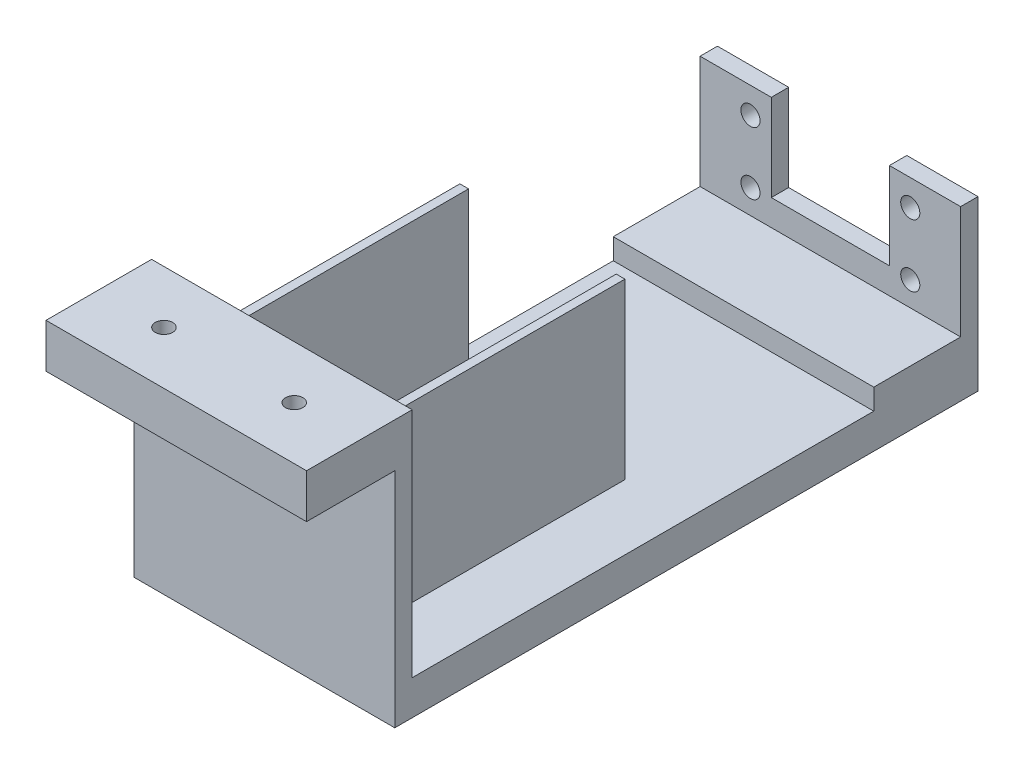
SolidWorks part; units mm, degrees
material "ABS"
ref_plane "Front Plane" through (0, 0, 0) normal (0, 0, 1) x (1, 0, 0)
ref_plane "Top Plane" through (0, 0, 0) normal (0, 1, 0) x (1, 0, 0)
ref_plane "Right Plane" through (0, 0, 0) normal (1, 0, 0) x (0, 0, -1)
sketch "Sketch1" plane through (0, 0, 0) normal (0, 0, 1) x (1, 0, 0)
  line L0 (20.5, 32.5) -> (20.5, 7.5)
  line L1 (0, 0) -> (75, 0)
  line L2 (0, 0) -> (0, 32.5)
  line L3 (0, 32.5) -> (75, 32.5)
  line L4 (75, 0) -> (75, 32.5)
  line L5 (20.5, 7.5) -> (54.5, 7.5)
  line L6 (54.5, 7.5) -> (54.5, 32.5)
  line L7 (37.5, 32.5) -> (37.5, 0) construction
  circle A0 centre (14.5, 25) radius 2.75
  circle A1 centre (14.5, 7) radius 2.75
  circle A2 centre (60.5, 7) radius 2.75
  circle A3 centre (60.5, 25) radius 2.75
  dimension "D6" = 5.5
  dimension "D7" = 46
  dimension "D8" = 34
  dimension "D1" = 32.5
  dimension "D2" = 75
  dimension "D3" = 17
  dimension "D4" = 18
  dimension "D5" = 25
  dimension "D9" = 25
  dimension "D10" = 14.5
  dimension "D11" = 6
extrude "Boss-Extrude1" add sketch "Sketch1" along normal blind 5 contours L7 L5 L0 L3 L2 L1 A1 A0 | L5 L7 L1 L4 L3 L6 A3 A2 region at (13.183, 14.1302, 0) region at (61.817, 14.1302, 0)
sketch "Sketch2" plane through (0, 0, 5) normal (0, 0, 1) x (1, 0, 0)
  line L0 (75, 0) -> (75, 32.5) construction
  line L1 (0, 0) -> (75, 0)
  line L2 (0, 0) -> (0, -6)
  line L3 (0, -6) -> (75, -6)
  line L4 (75, 0) -> (75, -6)
  dimension "D1" = 6
extrude "Boss-Extrude2" add sketch "Sketch2" along normal blind 25 and the other way blind 5
sketch "Sketch3" plane through (0, 0, 0) normal (0, 0, -1) x (-1, 0, 0)
  line L0 (0, -6) -> (0, 32.5) construction
  line L1 (-75, -6) -> (0, -6)
  line L2 (-75, -6) -> (-75, -16)
  line L3 (-75, -16) -> (0, -16)
  line L4 (0, -6) -> (0, -16)
  dimension "D1" = 10
extrude "Boss-Extrude3" add sketch "Sketch3" against normal blind 167.8942
sketch "Sketch4" plane through (0, -6, 0) normal (0, 1, 0) x (1, 0, 0)
  line L0 (75, -167.8942) -> (75, -30) construction
  line L1 (0, -167.8942) -> (75, -167.8942)
  line L2 (0, -167.8942) -> (0, -162.8942)
  line L3 (0, -162.8942) -> (75, -162.8942)
  line L4 (75, -167.8942) -> (75, -162.8942)
  dimension "D1" = 5
extrude "Boss-Extrude4" add sketch "Sketch4" along normal blind 66.8
sketch "Sketch5" plane through (0, 0, 167.8942) normal (0, 0, 1) x (1, 0, 0)
  line L0 (0, -16) -> (0, 60.8) construction
  line L1 (0, 48.1) -> (75, 48.1)
  line L2 (0, 48.1) -> (0, 60.8)
  line L3 (0, 60.8) -> (75, 60.8)
  line L4 (75, 48.1) -> (75, 60.8)
  line L5 (75, 60.8) -> (75, -16) construction
  line L6 (0, 60.8) -> (75, 60.8) construction
  dimension "D2" = 12.7
extrude "Boss-Extrude5" add sketch "Sketch5" along normal blind 25.4
sketch "Sketch6" plane through (0, 60.8, 0) normal (0, 1, 0) x (1, 0, 0)
  line L0 (0, -178.0942) -> (37.5, -178.0942) construction
  line L1 (37.5, -193.2942) -> (37.5, -162.8942) construction
  line L2 (75, -178.0942) -> (37.5, -178.0942) construction
  line L5 (0, -162.8942) -> (0, -193.2942)
  line L6 (0, -193.2942) -> (75, -193.2942)
  line L7 (75, -193.2942) -> (75, -162.8942)
  line L9 (0, -162.8942) -> (0, -193.2942)
  line L10 (0, -193.2942) -> (75, -193.2942)
  line L11 (75, -193.2942) -> (75, -162.8942)
  line L40 (75, -162.8942) -> (0, -162.8942)
  line L41 (75, -162.8942) -> (0, -162.8942)
  point P4 (18.75, -178.0942)
  point P10 (56.25, -178.0942)
  dimension "D1" = 0
hole_wizard "M5x0.8 Tapped Hole1" positions "Sketch6" profile "Sketch7" tap size "M5x0.8" standard "ANSI Metric" end condition through all
sketch "Sketch7" plane through (56.25, 60.8, 178.0942) normal (1, 0, 0) x (0, 0, 1)
  line L0 (0, 0) -> (0, 76.8)
  line L1 (0, 76.8) -> (2.5, 76.8)
  line L2 (2.5, 76.8) -> (2.5, 0)
  line L5 (2.5, 0) -> (0, 0)
  line L11 (0, -6.35) -> (0, 107.95) construction
  dimension "Thread Major Dia." = 5
  dimension "Thru Tap Drill Depth" = 76.8
sketch "Sketch8" plane through (0, 0, 162.8942) normal (0, 0, -1) x (-1, 0, 0)
  line L0 (-75, 27.4) -> (0, 27.4) construction
  line L1 (-75, 60.8) -> (-75, -6) construction
  line L2 (0, 60.8) -> (0, -6) construction
  line L3 (-58.75, 49) -> (-58.75, -1)
  line L4 (-58.75, 49) -> (-61.25, 49)
  line L5 (-37.5, 60.8) -> (-37.5, -6) construction
  line L6 (-75, 60.8) -> (0, 60.8) construction
  line L7 (-75, -6) -> (0, -6) construction
  line L8 (-61.25, 49) -> (-61.25, -1)
  line L9 (-61.25, -1) -> (-58.75, -1)
  line L10 (-13.75, -1) -> (-16.25, -1)
  line L11 (-16.25, 49) -> (-16.25, -1)
  line L12 (-16.25, 49) -> (-13.75, 49)
  line L13 (-13.75, 49) -> (-13.75, -1)
  point P20 (0, 0)
  dimension "D1" = 42.5
  dimension "D2" = 2.5
  dimension "D3" = 50
  dimension "D4" = 5
extrude "Boss-Extrude6" add sketch "Sketch8" along normal blind 75
